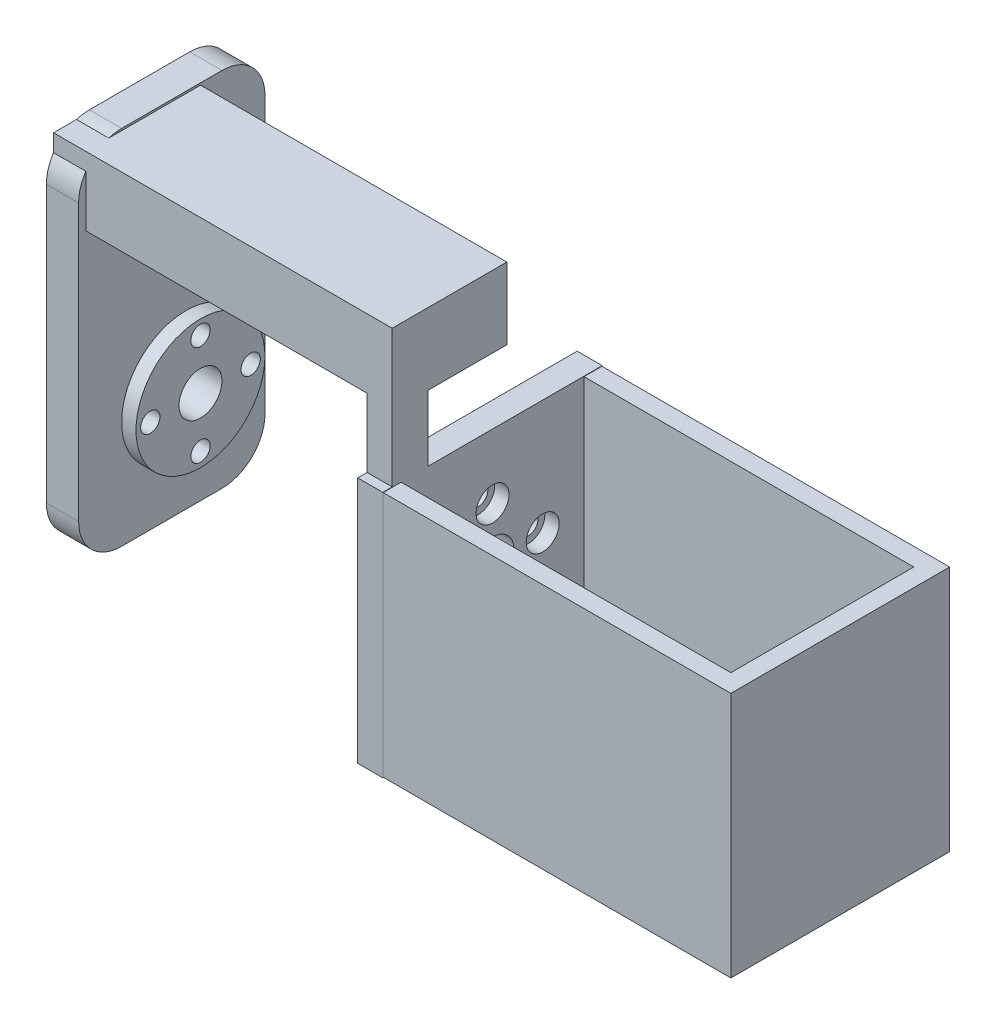
SolidWorks part; units mm, degrees
ref_plane "Front Plane" through (0, 0, 0) normal (0, 0, 1) x (1, 0, 0)
ref_plane "Top Plane" through (0, 0, 0) normal (0, 1, 0) x (1, 0, 0)
ref_plane "Right Plane" through (0, 0, 0) normal (1, 0, 0) x (0, 0, -1)
ref_plane "PX_m14_010" through (-14.01, 0, 0) normal (1, 0, 0) x (0, 0, -1)
sketch "S_prism1" plane through (-14.01, 0, 0) normal (1, 0, 0) x (0, 0, -1)
  line L0 (15.31, -18.45) -> (15.31, 16.05)
  line L1 (15.31, 16.05) -> (-15.31, 16.05)
  line L2 (-15.31, 16.05) -> (-15.31, -18.45)
  line L3 (-15.31, -18.45) -> (15.31, -18.45)
extrude "Boss_1" add sketch "S_prism1" along normal blind 3.5
ref_plane "PX_m53_260" through (-53.26, 0, 0) normal (1, 0, 0) x (0, 0, -1)
sketch "S_cyl2" plane through (-53.26, 0, 0) normal (1, 0, 0) x (0, 0, -1)
  circle A0 centre (0, 0) radius 9
  dimension "D1_S_cyl2" = 18
extrude "Boss_2" add sketch "S_cyl2" along normal blind 2
ref_plane "PX_m57_760" through (-57.76, 0, 0) normal (1, 0, 0) x (0, 0, -1)
sketch "S_prism3" plane through (-57.76, 0, 0) normal (1, 0, 0) x (0, 0, -1)
  line L0 (11, -9) -> (11, 29.5)
  line L1 (5, 35.5) -> (-9, 35.5)
  line L2 (-15, 29.5) -> (-15, -9)
  line L3 (-9, -15) -> (5, -15)
  arc A0 (5, -15) -> (11, -9) centre (4.9999, -8.9999) ccw
  arc A1 (11, 29.5) -> (5, 35.5) centre (4.9999, 29.4999) ccw
  arc A2 (-9, 35.5) -> (-15, 29.5) centre (-8.9999, 29.4999) ccw
  arc A3 (-15, -9) -> (-9, -15) centre (-8.9999, -8.9999) ccw
extrude "Boss_3" add sketch "S_prism3" along normal blind 4.5
ref_plane "PZ_m15_260" through (0, 0, -15.26) normal (0, 0, 1) x (1, 0, 0)
sketch "S_box4" plane through (0, 0, -15.26) normal (0, 0, 1) x (1, 0, 0)
  line L0 (-13.01, -18.4) -> (-10.51, -18.4)
  line L1 (-10.51, -18.4) -> (-10.51, 16)
  line L2 (-10.51, 16) -> (-13.01, 16)
  line L3 (-13.01, 16) -> (-13.01, -18.4)
  dimension "P1" = 13.01
  dimension "P2" = 18.4
  dimension "P3" = 10.51
  dimension "P4" = 18.4
  dimension "P5" = 10.51
  dimension "P6" = 16
  dimension "P7" = 13.01
  dimension "P8" = 16
extrude "Boss_4" add sketch "S_box4" along normal blind 30.52
sketch "S_box5" plane through (0, 0, -15.26) normal (0, 0, 1) x (1, 0, 0)
  line L0 (35.51, -18.4) -> (38.01, -18.4)
  line L1 (38.01, -18.4) -> (38.01, 16)
  line L2 (38.01, 16) -> (35.51, 16)
  line L3 (35.51, 16) -> (35.51, -18.4)
  dimension "P1" = 35.51
  dimension "P2" = 18.4
  dimension "P3" = 38.01
  dimension "P4" = 18.4
  dimension "P5" = 38.01
  dimension "P6" = 16
  dimension "P7" = 35.51
  dimension "P8" = 16
extrude "Boss_5" add sketch "S_box5" along normal blind 30.52
sketch "S_box6" plane through (0, 0, -15.26) normal (0, 0, 1) x (1, 0, 0)
  line L0 (-13.01, -18.4) -> (38.01, -18.4)
  line L1 (38.01, -18.4) -> (38.01, 16)
  line L2 (38.01, 16) -> (-13.01, 16)
  line L3 (-13.01, 16) -> (-13.01, -18.4)
  dimension "P1" = 13.01
  dimension "P2" = 18.4
  dimension "P3" = 38.01
  dimension "P4" = 18.4
  dimension "P5" = 38.01
  dimension "P6" = 16
  dimension "P7" = 13.01
  dimension "P8" = 16
extrude "Boss_6" add sketch "S_box6" along normal blind 2.5
ref_plane "PZ_p12_760" through (0, 0, 12.76) normal (0, 0, 1) x (1, 0, 0)
sketch "S_box7" plane through (0, 0, 12.76) normal (0, 0, 1) x (1, 0, 0)
  line L0 (-13.01, -18.4) -> (38.01, -18.4)
  line L1 (38.01, -18.4) -> (38.01, 16)
  line L2 (38.01, 16) -> (-13.01, 16)
  line L3 (-13.01, 16) -> (-13.01, -18.4)
  dimension "P1" = 13.01
  dimension "P2" = 18.4
  dimension "P3" = 38.01
  dimension "P4" = 18.4
  dimension "P5" = 38.01
  dimension "P6" = 16
  dimension "P7" = 13.01
  dimension "P8" = 16
extrude "Boss_7" add sketch "S_box7" along normal blind 2.5
sketch "S_box8" plane through (0, 0, -15.26) normal (0, 0, 1) x (1, 0, 0)
  line L0 (-13.01, -18.4) -> (38.01, -18.4)
  line L1 (38.01, -18.4) -> (38.01, -16)
  line L2 (38.01, -16) -> (-13.01, -16)
  line L3 (-13.01, -16) -> (-13.01, -18.4)
  dimension "P1" = 13.01
  dimension "P2" = 18.4
  dimension "P3" = 38.01
  dimension "P4" = 18.4
  dimension "P5" = 38.01
  dimension "P6" = 16
  dimension "P7" = 13.01
  dimension "P8" = 16
extrude "Boss_8" add sketch "S_box8" along normal blind 30.52
ref_plane "PZ_p9_000" through (0, 0, 9) normal (0, 0, 1) x (1, 0, 0)
sketch "S_box9" plane through (0, 0, 9) normal (0, 0, 1) x (1, 0, 0)
  line L0 (-14.01, 16) -> (-10.51, 16)
  line L1 (-10.51, 16) -> (-10.51, 25.725)
  line L2 (-10.51, 25.725) -> (-14.01, 25.725)
  line L3 (-14.01, 25.725) -> (-14.01, 16)
  dimension "P1" = 14.01
  dimension "P2" = 16
  dimension "P3" = 10.51
  dimension "P4" = 16
  dimension "P5" = 10.51
  dimension "P6" = 25.725
  dimension "P7" = 14.01
  dimension "P8" = 25.725
extrude "Boss_9" add sketch "S_box9" along normal blind 5
ref_plane "PZ_m2_000" through (0, 0, -2) normal (0, 0, 1) x (1, 0, 0)
sketch "S_box10" plane through (0, 0, -2) normal (0, 0, 1) x (1, 0, 0)
  line L0 (-14.01, 25.225) -> (-10.51, 25.225)
  line L1 (-10.51, 25.225) -> (-10.51, 35.225)
  line L2 (-10.51, 35.225) -> (-14.01, 35.225)
  line L3 (-14.01, 35.225) -> (-14.01, 25.225)
  dimension "P1" = 14.01
  dimension "P2" = 25.225
  dimension "P3" = 10.51
  dimension "P4" = 25.225
  dimension "P5" = 10.51
  dimension "P6" = 35.225
  dimension "P7" = 14.01
  dimension "P8" = 35.225
extrude "Boss_10" add sketch "S_box10" along normal blind 16
sketch "S_box11" plane through (0, 0, -2) normal (0, 0, 1) x (1, 0, 0)
  line L0 (-57.76, 25.625) -> (-10.51, 25.625)
  line L1 (-10.51, 25.625) -> (-10.51, 35.225)
  line L2 (-10.51, 35.225) -> (-57.76, 35.225)
  line L3 (-57.76, 35.225) -> (-57.76, 25.625)
  dimension "P1" = 57.76
  dimension "P2" = 25.625
  dimension "P3" = 10.51
  dimension "P4" = 25.625
  dimension "P5" = 10.51
  dimension "P6" = 35.225
  dimension "P7" = 57.76
  dimension "P8" = 35.225
extrude "Boss_11" add sketch "S_box11" along normal blind 16
ref_plane "PX_m14_110" through (-14.11, 0, 0) normal (1, 0, 0) x (0, 0, -1)
sketch "S_hole12" plane through (-14.11, 0, 0) normal (1, 0, 0) x (0, 0, -1)
  circle A0 centre (0, 0) radius 3
  dimension "D1_S_hole12" = 6
extrude "Hole_12" cut sketch "S_hole12" along normal blind 3.7
sketch "S_hole13" plane through (-14.11, 0, 0) normal (1, 0, 0) x (0, 0, -1)
  circle A0 centre (0, 7) radius 1.35
  dimension "D1_S_hole13" = 2.7
  dimension "P2" = 7
extrude "Hole_13" cut sketch "S_hole13" along normal blind 3.7
sketch "S_hole14" plane through (-14.11, 0, 0) normal (1, 0, 0) x (0, 0, -1)
  circle A0 centre (-7, 0) radius 1.35
  dimension "D1_S_hole14" = 2.7
  dimension "P2" = 7
extrude "Hole_14" cut sketch "S_hole14" along normal blind 3.7
sketch "S_hole15" plane through (-14.11, 0, 0) normal (1, 0, 0) x (0, 0, -1)
  circle A0 centre (0, -7) radius 1.35
  dimension "D1_S_hole15" = 2.7
  dimension "P2" = 7
extrude "Hole_15" cut sketch "S_hole15" along normal blind 3.7
sketch "S_hole16" plane through (-14.11, 0, 0) normal (1, 0, 0) x (0, 0, -1)
  circle A0 centre (7, 0) radius 1.35
  dimension "D1_S_hole16" = 2.7
  dimension "P2" = 7
extrude "Hole_16" cut sketch "S_hole16" along normal blind 3.7
ref_plane "PX_m57_860" through (-57.86, 0, 0) normal (1, 0, 0) x (0, 0, -1)
sketch "S_hole17" plane through (-57.86, 0, 0) normal (1, 0, 0) x (0, 0, -1)
  circle A0 centre (0, 0) radius 3
  dimension "D1_S_hole17" = 6
extrude "Hole_17" cut sketch "S_hole17" along normal blind 6.7
sketch "S_hole18" plane through (-57.86, 0, 0) normal (1, 0, 0) x (0, 0, -1)
  circle A0 centre (0, 7) radius 1.35
  dimension "D1_S_hole18" = 2.7
  dimension "P2" = 7
extrude "Hole_18" cut sketch "S_hole18" along normal blind 6.7
sketch "S_hole19" plane through (-57.86, 0, 0) normal (1, 0, 0) x (0, 0, -1)
  circle A0 centre (-7, 0) radius 1.35
  dimension "D1_S_hole19" = 2.7
  dimension "P2" = 7
extrude "Hole_19" cut sketch "S_hole19" along normal blind 6.7
sketch "S_hole20" plane through (-57.86, 0, 0) normal (1, 0, 0) x (0, 0, -1)
  circle A0 centre (0, -7) radius 1.35
  dimension "D1_S_hole20" = 2.7
  dimension "P2" = 7
extrude "Hole_20" cut sketch "S_hole20" along normal blind 6.7
sketch "S_hole21" plane through (-57.86, 0, 0) normal (1, 0, 0) x (0, 0, -1)
  circle A0 centre (7, 0) radius 1.35
  dimension "D1_S_hole21" = 2.7
  dimension "P2" = 7
extrude "Hole_21" cut sketch "S_hole21" along normal blind 6.7
ref_plane "PY_m18_500" through (0, -18.5, 0) normal (0, 1, 0) x (1, 0, 0)
sketch "S_hole22" plane through (0, -18.5, 0) normal (0, 1, 0) x (1, 0, 0)
  circle A0 centre (0, 0) radius 11
  dimension "D1_S_hole22" = 22
extrude "Hole_22" cut sketch "S_hole22" along normal blind 2.6
sketch "S_hole23" plane through (0, -18.5, 0) normal (0, 1, 0) x (1, 0, 0)
  circle A0 centre (8.3, -10.25) radius 1.1
  dimension "D1_S_hole23" = 2.2
  dimension "P2" = 8.3
  dimension "P3" = 10.25
extrude "Hole_23" cut sketch "S_hole23" along normal blind 2.6
sketch "S_hole24" plane through (0, -18.5, 0) normal (0, 1, 0) x (1, 0, 0)
  circle A0 centre (32.75, 10.25) radius 1.1
  dimension "D1_S_hole24" = 2.2
  dimension "P2" = 32.75
  dimension "P3" = 10.25
extrude "Hole_24" cut sketch "S_hole24" along normal blind 2.6
sketch "S_hole25" plane through (0, -18.5, 0) normal (0, 1, 0) x (1, 0, 0)
  circle A0 centre (32.75, -10.25) radius 1.1
  dimension "D1_S_hole25" = 2.2
  dimension "P2" = 32.75
  dimension "P3" = 10.25
extrude "Hole_25" cut sketch "S_hole25" along normal blind 2.6
ref_plane "PX_m12_510" through (-12.51, 0, 0) normal (1, 0, 0) x (0, 0, -1)
sketch "S_hole26" plane through (-12.51, 0, 0) normal (1, 0, 0) x (0, 0, -1)
  circle A0 centre (0, 7) radius 2.3
  dimension "D1_S_hole26" = 4.6
  dimension "P2" = 7
extrude "Hole_26" cut sketch "S_hole26" along normal blind 2.1
sketch "S_hole27" plane through (-12.51, 0, 0) normal (1, 0, 0) x (0, 0, -1)
  circle A0 centre (-7, 0) radius 2.3
  dimension "D1_S_hole27" = 4.6
  dimension "P2" = 7
extrude "Hole_27" cut sketch "S_hole27" along normal blind 2.1
sketch "S_hole28" plane through (-12.51, 0, 0) normal (1, 0, 0) x (0, 0, -1)
  circle A0 centre (0, -7) radius 2.3
  dimension "D1_S_hole28" = 4.6
  dimension "P2" = 7
extrude "Hole_28" cut sketch "S_hole28" along normal blind 2.1
sketch "S_hole29" plane through (-12.51, 0, 0) normal (1, 0, 0) x (0, 0, -1)
  circle A0 centre (7, 0) radius 2.3
  dimension "D1_S_hole29" = 4.6
  dimension "P2" = 7
extrude "Hole_29" cut sketch "S_hole29" along normal blind 2.1
equation "\"plate_t\" = 3"
equation "\"clearance\" = 0.4"
